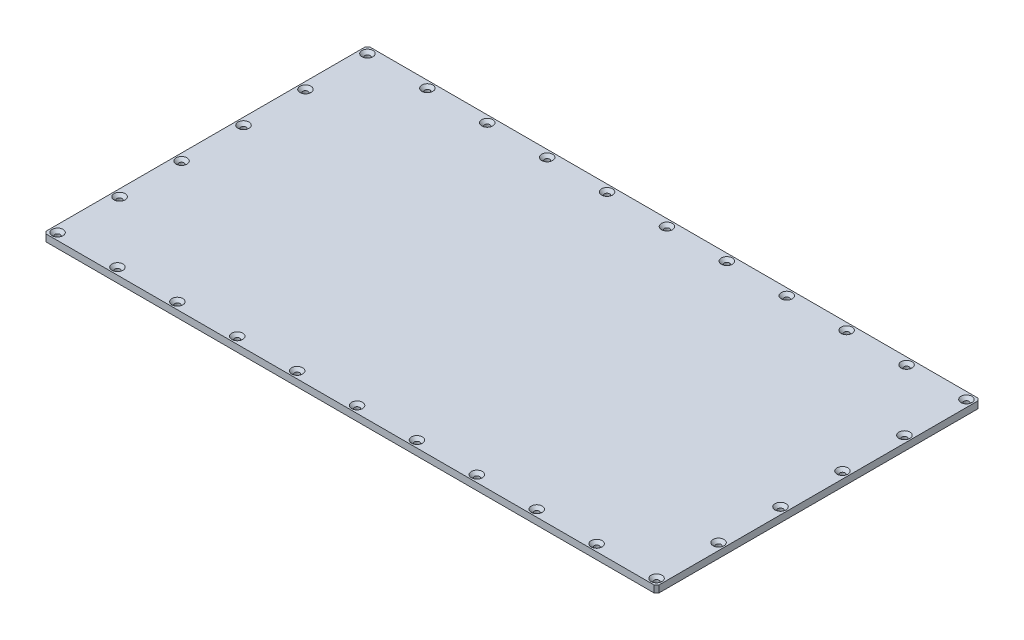
SolidWorks part; units mm, degrees
ref_plane "Front Plane" through (0, 0, 0) normal (0, 0, 1) x (1, 0, 0)
ref_plane "Top Plane" through (0, 0, 0) normal (0, 1, 0) x (1, 0, 0)
ref_plane "Right Plane" through (0, 0, 0) normal (1, 0, 0) x (0, 0, -1)
sketch "Sketch1" plane through (0, 0, 0) normal (0, 1, 0) x (1, 0, 0)
  line L0 (265, -131.75) -> (265, 0)
  line L1 (0, -140) -> (265, -140)
  line L2 (0, -140) -> (0, 0)
  line L3 (0, 0) -> (265, 0)
  line L4 (265, -140) -> (265, -136.25)
  circle A0 centre (6, -26.8) radius 2.25
  circle A1 centre (6, -80.4) radius 2.25
  circle A2 centre (6, -134) radius 2.25
  circle A3 centre (57.8, -134) radius 2.25
  circle A4 centre (109.6, -134) radius 2.25
  circle A5 centre (161.4, -134) radius 2.25
  circle A6 centre (213.2, -134) radius 2.25
  arc A7 (265, -131.75) -> (265, -136.25) centre (265, -134) ccw
  dimension "D3" = 4.5
  dimension "D4" = 4.5
  dimension "D5" = 4.5
  dimension "D6" = 4.5
  dimension "D7" = 4.5
  dimension "D8" = 4.5
  dimension "D9" = 4.5
  dimension "D18" = 4.5
  dimension "D1" = 265
  dimension "D2" = 140
  dimension "D10" = 6
  dimension "D11" = 6
  dimension "D12" = 6
  dimension "D13" = 6
  dimension "D14" = 6
  dimension "D15" = 6
  dimension "D16" = 6
  dimension "D17" = 6
  dimension "D19" = 6
  dimension "D20" = 51.8
  dimension "D21" = 51.8
  dimension "D22" = 51.8
  dimension "D23" = 51.8
  dimension "D24" = 53.6
  dimension "D25" = 53.6
  dimension "D26" = 0
  dimension "D27" = 0
extrude "Boss-Extrude1" add sketch "Sketch1" along normal blind 6 contours L2 L3 L0 A7 L4 L1 | A3 | A4 | A2 | A1 | A0 | A6 | A5
chamfer "Chamfer1" distance 2.5 angle 45 8 edges at (6, 6, 29.05) (6, 6, 82.65) (6, 6, 136.25) (57.8, 6, 136.25) (109.6, 6, 136.25) (161.4, 6, 136.25) (213.2, 6, 136.25) (262.75, 6, 134)
mirror "Mirror3" about plane through (265, 6, 131.75) normal (-1, 0, 0) of bodies 101
mirror "Mirror4" about plane through (0, 6, 0) normal (0, 0, -1) of bodies 104
chamfer "Chamfer2" distance 2 angle 45 4 edges at (0, 3, -140) (0, 3, 140) (530, 3, -140) (530, 3, 140)
equation "\"D4@Sketch1\"=\"D3@Sketch1\""
equation "\"D5@Sketch1\"=\"D3@Sketch1\""
equation "\"D6@Sketch1\"=\"D3@Sketch1\""
equation "\"D7@Sketch1\"=\"D3@Sketch1\""
equation "\"D8@Sketch1\"=\"D3@Sketch1\""
equation "\"D9@Sketch1\"=\"D3@Sketch1\""
equation "\"D18@Sketch1\"=\"D3@Sketch1\""
